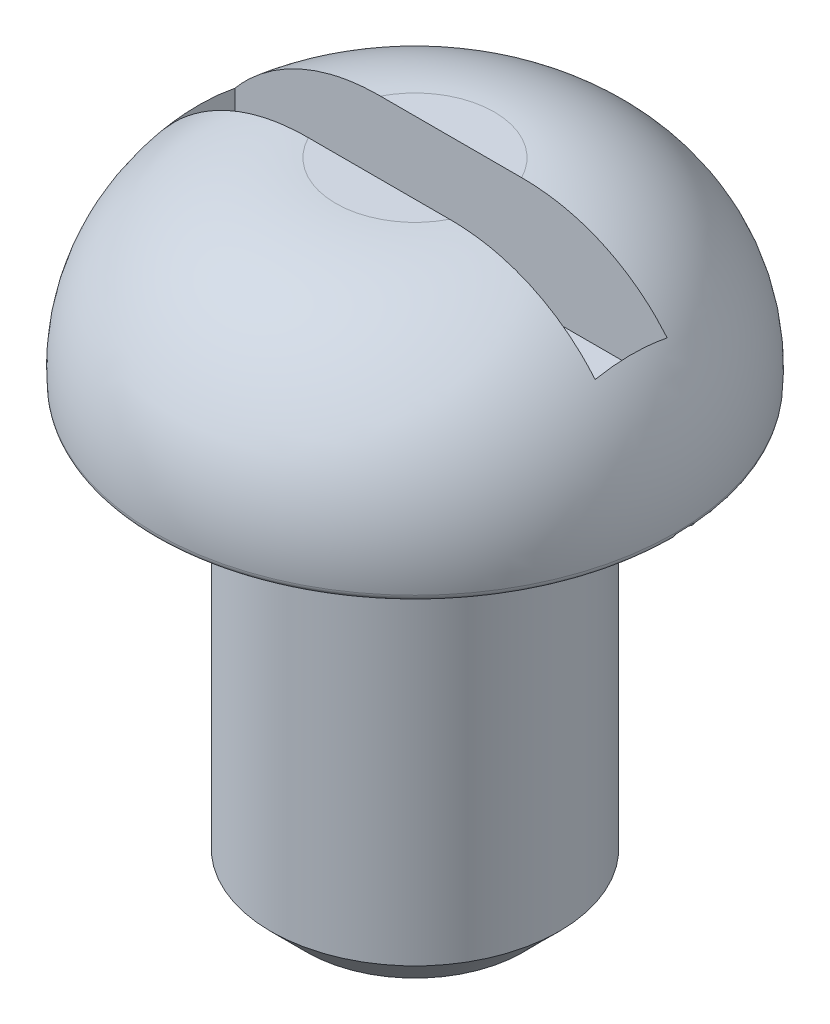
SolidWorks part; units mm, degrees
ref_plane "Спереди" through (0, 0, 0) normal (0, 0, 1) x (1, 0, 0)
ref_plane "Сверху" through (0, 0, 0) normal (0, 1, 0) x (1, 0, 0)
ref_plane "Справа" through (0, 0, 0) normal (1, 0, 0) x (0, 0, -1)
sketch "Эскиз1" plane through (0, 0, 0) normal (0, 0, 1) x (1, 0, 0)
  line L0 (3.6, 6) -> (2, 6)
  line L1 (0, 0) -> (0, 8.8)
  line L2 (2, 6) -> (2, 0.5)
  line L3 (2, 0.5) -> (1.5, 0)
  line L4 (1.5, 0) -> (0, 0)
  line L5 (0, 8.8) -> (1.1, 8.8)
  arc A0 (1.1, 8.8) -> (3.6, 6) centre (1.1, 6.2839) cw
  dimension "D2" = 1.1
  dimension "D1" = 6
  dimension "D3" = 2
  dimension "D4" = 1.5
  dimension "D5" = 2.8
  dimension "D6" = 3.6
  dimension "D7" = 45
revolve "Повернуть1" add sketch "Эскиз1" angle 360 about L1
fillet "Скругление1" radius 0.1 1 edges at (0, 6, -3.6)
sketch "Эскиз3" plane through (0, 8.8, 0) normal (0, 1, 0) x (-1, 0, 0)
  line L1 (3, -0.5) -> (-3, -0.5)
  line L2 (3, -0.5) -> (3, 0.5)
  line L3 (3, 0.5) -> (-3, 0.5)
  line L4 (-3, -0.5) -> (-3, 0.5)
  dimension "D1" = 1
  dimension "D2" = 0.5
  dimension "D3" = 6
  dimension "D4" = 3
extrude "Вырез-Вытянуть2" cut sketch "Эскиз3" against normal blind 1.5
ref_axis "Ось1" through (0, -104.1565, 0) along (0, 1, 0)
